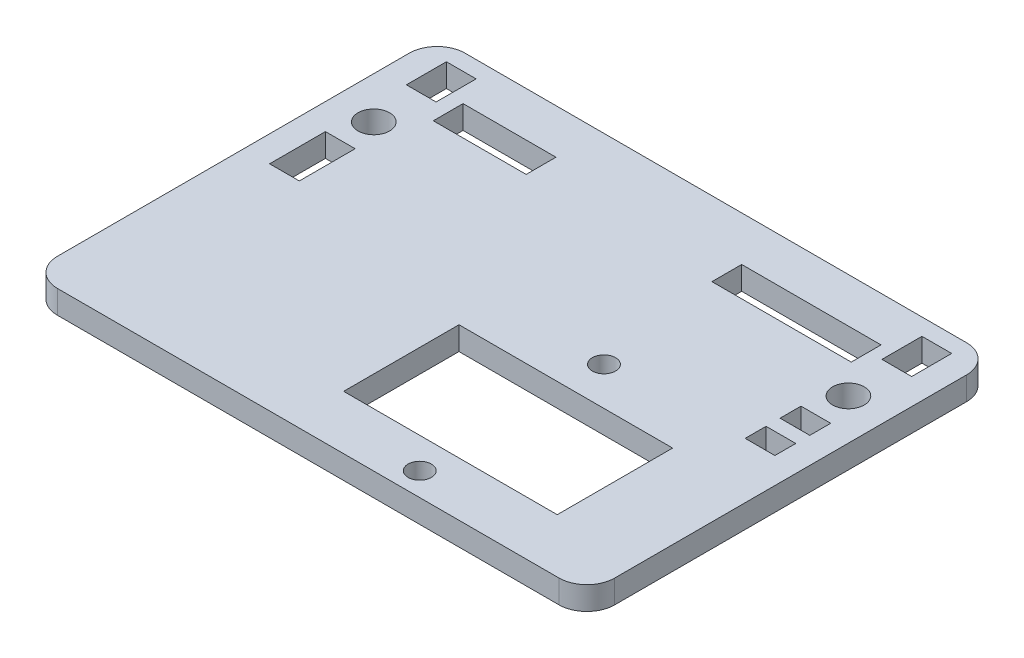
SolidWorks part; units mm, degrees
material "Acrylic (Medium-high impact)"
ref_plane "Front Plane" through (0, 0, 0) normal (0, 0, 1) x (1, 0, 0)
ref_plane "Top Plane" through (0, 0, 0) normal (0, 1, 0) x (1, 0, 0)
ref_plane "Right Plane" through (0, 0, 0) normal (1, 0, 0) x (0, 0, -1)
sketch "Sketch1" plane through (0, 0, 0) normal (0, 1, 0) x (1, 0, 0)
  line L0 (-8.8986, 14.6168) -> (-8.8988, -23.1844)
  line L1 (48.1999, -0.9368) -> (48.1999, -3.1838)
  line L2 (48.1999, -3.1838) -> (45.0054, -3.1838)
  line L3 (45.0054, -3.1838) -> (45.0054, -0.9368)
  line L4 (45.0054, -0.9368) -> (48.1999, -0.9368)
  line L5 (-6.104, 2.8166) -> (-6.104, -3.1836)
  line L6 (-6.104, -3.1836) -> (-2.9098, -3.1836)
  line L7 (-2.9098, -3.1836) -> (-2.9098, 2.8166)
  line L8 (-2.9098, 2.8166) -> (-6.104, 2.8166)
  line L9 (28.6345, 12.8168) -> (43.608, 12.8168)
  line L10 (43.608, 12.8168) -> (43.608, 9.6168)
  line L11 (43.608, 9.6168) -> (28.6345, 9.6168)
  line L12 (28.6345, 9.6168) -> (28.6345, 12.8168)
  line L13 (8.6699, 12.8168) -> (8.6699, 9.6168)
  line L14 (8.6699, 9.6168) -> (-1.3122, 9.6168)
  line L15 (-1.3122, 9.6168) -> (-1.3122, 12.8168)
  line L16 (-1.3122, 12.8168) -> (8.6699, 12.8168)
  line L17 (-5.8986, -26.1846) -> (48.0001, -26.1846)
  line L18 (50.9948, -23.1899) -> (50.9948, 14.6168)
  line L19 (47.9947, 17.6169) -> (-5.9041, 17.6169)
  line L20 (-6.1038, 11.5167) -> (-6.1038, 15.817)
  line L21 (-6.1038, 15.817) -> (-2.9096, 15.817)
  line L22 (-2.9096, 15.817) -> (-2.9096, 11.5167)
  line L23 (-2.9096, 11.5167) -> (-6.1038, 11.5167)
  line L24 (45.0054, 0.5694) -> (45.0054, 2.8164)
  line L25 (45.0054, 2.8164) -> (48.1999, 2.8164)
  line L26 (48.1999, 2.8164) -> (48.1999, 0.5694)
  line L27 (48.1999, 0.5694) -> (45.0054, 0.5694)
  line L28 (48.1999, 15.817) -> (48.1999, 11.5167)
  line L29 (48.1999, 11.5167) -> (45.0054, 11.5167)
  line L30 (45.0054, 11.5167) -> (45.0054, 15.817)
  line L31 (45.0054, 15.817) -> (48.1999, 15.817)
  line L32 (42.0107, -7.9839) -> (19.0516, -7.9839)
  line L33 (19.0516, -7.9839) -> (19.0516, -20.3844)
  line L34 (19.0516, -20.3844) -> (42.0107, -20.3844)
  line L35 (42.0107, -20.3844) -> (42.0107, -7.9839)
  arc A0 (-5.9041, 17.6169) -> (-8.8986, 14.6168) centre (-5.9041, 14.6224) ccw
  arc A1 (-8.8988, -23.1844) -> (-5.8986, -26.1846) centre (-5.8986, -23.1844) ccw
  arc A2 (48.0001, -26.1846) -> (50.9948, -23.1899) centre (48.0001, -23.1899) ccw
  arc A3 (50.9948, 14.6168) -> (47.9947, 17.6169) centre (47.9947, 14.6168) ccw
  circle A4 centre (-4.4068, 6.3166) radius 1.7
  circle A5 centre (30.5312, -3.8842) radius 1.25
  circle A6 centre (46.6027, 6.3164) radius 1.7
  circle A7 centre (30.5312, -23.6847) radius 1.25
  point P29 (-4.4068, 6.3166)
  point P32 (30.5312, -23.6847)
  point P35 (46.6027, 6.3164)
  point P42 (30.5312, -3.8842)
  dimension "D1" = 3.4
  dimension "D4" = 2.5
  dimension "D2" = 22.9592
  dimension "D3" = 12.4005
extrude "Boss-Extrude1" add sketch "Sketch1" along normal blind 2.5
equation "\"0.025inin\"=0.045"
